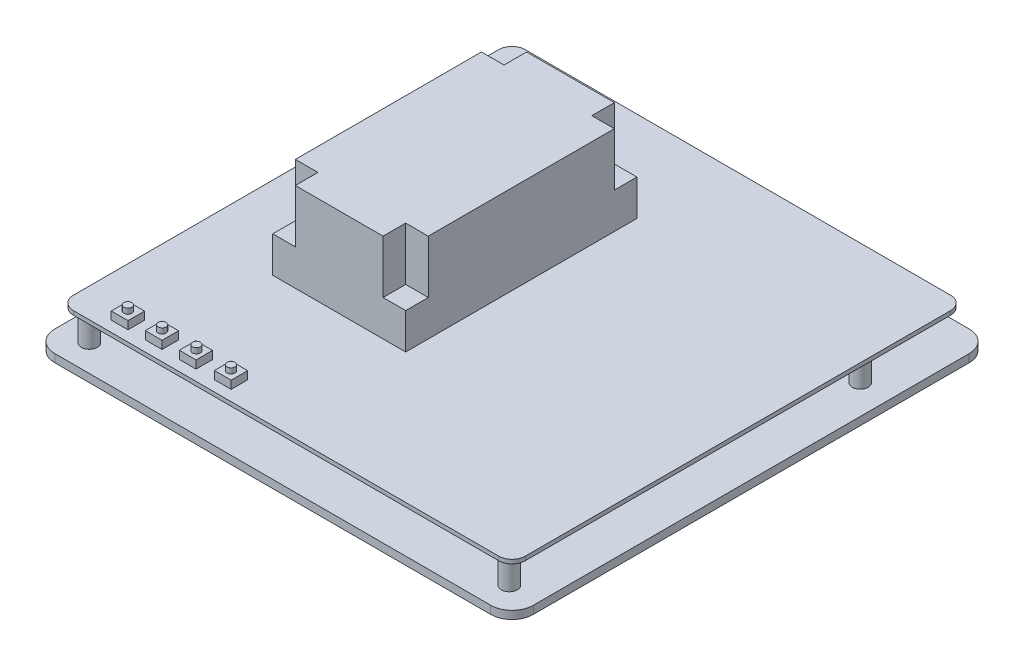
SolidWorks part; units mm, degrees
ref_plane "Plano frontal" through (0, 0, 0) normal (0, 0, 1) x (1, 0, 0)
ref_plane "Plano superior" through (0, 0, 0) normal (0, 1, 0) x (1, 0, 0)
ref_plane "Plano direito" through (0, 0, 0) normal (1, 0, 0) x (0, 0, -1)
sketch "Esboço1" plane through (0, 0, 0) normal (0, 1, 0) x (1, 0, 0)
  line L1 (82, -90) -> (-82, -90)
  line L2 (90, -82) -> (90, 82)
  line L3 (82, 90) -> (-82, 90)
  line L4 (-90, -82) -> (-90, 82)
  line L5 (90, -90) -> (-90, 90) construction
  line L6 (90, 90) -> (-90, -90) construction
  arc A0 (82, -90) -> (90, -82) centre (82, -82) ccw
  arc A1 (-82, -90) -> (-90, -82) centre (-82, -82) cw
  arc A2 (90, 82) -> (82, 90) centre (82, 82) ccw
  arc A3 (-82, 90) -> (-90, 82) centre (-82, 82) ccw
  point P0 (0, 0)
  dimension "D3" = 8
  dimension "D1" = 180
  dimension "D2" = 180
extrude "Ressalto-extrusão1" add sketch "Esboço1" along normal blind 3
sketch "Esboço2" plane through (0, 0, 0) normal (0, -1, 0) x (-1, 0, 0)
  line L0 (82, -90) -> (-82, -90) construction
  line L1 (90, 82) -> (90, -82) construction
  line L2 (0, 0) -> (-90, 0) construction
  line L3 (-90, -82) -> (-90, 82) construction
  line L4 (0, 0) -> (0, -90) construction
  circle A0 centre (79, -62) radius 3.5
  circle A1 centre (-79, -62) radius 3.5
  circle A2 centre (-79, 62) radius 3.5
  circle A3 centre (79, 62) radius 3.5
  dimension "D1" = 7
  dimension "D2" = 28
  dimension "D3" = 11
extrude "Ressalto-extrusão2" add sketch "Esboço2" along normal blind 5
sketch "Esboço3" plane through (0, 3, 0) normal (0, 1, 0) x (1, 0, 0)
  line L0 (90, -82) -> (90, 82) construction
  line L1 (-82, -90) -> (82, -90) construction
  line L2 (-90, 82) -> (-90, -82) construction
  line L3 (82, 90) -> (-82, 90) construction
  circle A0 centre (-79, -80) radius 3
  circle A1 centre (-79, 75) radius 3
  circle A2 centre (79, 52) radius 3
  circle A3 centre (79, -80) radius 3
  dimension "D1" = 6
  dimension "D3" = 11
  dimension "D5" = 10
  dimension "D6" = 38
  dimension "D2" = 10
  dimension "D4" = 11
  dimension "D7" = 15
extrude "Ressalto-extrusão3" add sketch "Esboço3" along normal blind 11
sketch "Esboço4" plane through (0, 14, 0) normal (0, 1, 0) x (1, 0, 0)
  line L1 (-80, 85) -> (80, 85)
  line L2 (-85, 80) -> (-85, -80)
  line L3 (-80, -85) -> (80, -85)
  line L4 (85, 80) -> (85, -80)
  line L5 (-85, 85) -> (85, -85) construction
  line L6 (-85, -85) -> (85, 85) construction
  arc A1 (80, -85) -> (85, -80) centre (80, -80) ccw
  arc A2 (-85, -80) -> (-80, -85) centre (-80, -80) ccw
  arc A3 (80, 85) -> (85, 80) centre (80, 80) cw
  arc A4 (-80, 85) -> (-85, 80) centre (-80, 80) ccw
  point P0 (0, 0)
  dimension "D3" = 5
  dimension "D1" = 170
  dimension "D2" = 170
extrude "Ressalto-extrusão4" add sketch "Esboço4" along normal blind 1.5
sketch "Esboço5" plane through (0, 15.5, 0) normal (0, 1, 0) x (1, 0, 0)
  line L0 (-80, -85) -> (80, -85) construction
  line L1 (-54, 51) -> (-4, 51)
  line L2 (-54, 51) -> (-54, -36)
  line L3 (-54, -36) -> (-4, -36)
  line L4 (-4, 51) -> (-4, -36)
  line L5 (-54, 51) -> (-4, -36) construction
  line L6 (-54, -36) -> (-4, 51) construction
  line L7 (-85, 80) -> (-85, -80) construction
  point P0 (-29, 7.5)
  point P5 (-51.8016, -21.9685)
  point P6 (-53.8976, -29.5663)
  dimension "D1" = 50
  dimension "D2" = 87
  dimension "D3" = 49
  dimension "D4" = 31
extrude "Ressalto-extrusão5" add sketch "Esboço5" along normal blind 33.5
sketch "Esboço6" plane through (0, 49, 0) normal (0, 1, 0) x (1, 0, 0)
  line L0 (-54, 7.5) -> (-4, 7.5) construction
  line L1 (-54, -36) -> (-45.5, -36)
  line L2 (-54, -36) -> (-54, -27.5)
  line L3 (-54, -27.5) -> (-45.5, -27.5)
  line L4 (-45.5, -36) -> (-45.5, -27.5)
  line L5 (-54, 51) -> (-54, -36) construction
  line L6 (-4, -36) -> (-4, 51) construction
  line L7 (-29, 51) -> (-29, -36) construction
  line L8 (-4, 51) -> (-54, 51) construction
  line L9 (-54, -36) -> (-4, -36) construction
  line L10 (-12.5, -36) -> (-12.5, -27.5)
  line L11 (-4, -36) -> (-12.5, -36)
  line L12 (-4, -36) -> (-4, -27.5)
  line L13 (-4, -27.5) -> (-12.5, -27.5)
  line L14 (-4, 42.5) -> (-12.5, 42.5)
  line L15 (-4, 51) -> (-4, 42.5)
  line L16 (-4, 51) -> (-12.5, 51)
  line L17 (-12.5, 51) -> (-12.5, 42.5)
  line L18 (-45.5, 51) -> (-45.5, 42.5)
  line L19 (-54, 42.5) -> (-45.5, 42.5)
  line L20 (-54, 51) -> (-54, 42.5)
  line L21 (-54, 51) -> (-45.5, 51)
  dimension "D1" = 8.5
  dimension "D2" = 8.5
extrude "Corte-extrusão1" cut sketch "Esboço6" against normal blind 20
sketch "Esboço7" plane through (0, 15.5, 0) normal (0, 1, 0) x (1, 0, 0)
  line L0 (-30.95, -74.8) -> (-24.65, -74.8)
  line L1 (-69.75, -74.8) -> (-63.45, -74.8)
  line L2 (-69.75, -74.8) -> (-69.75, -81)
  line L3 (-69.75, -81) -> (-63.45, -81)
  line L4 (-63.45, -74.8) -> (-63.45, -81)
  line L5 (-69.75, -74.8) -> (-63.45, -81) construction
  line L6 (-69.75, -81) -> (-63.45, -74.8) construction
  line L7 (-80, -85) -> (80, -85) construction
  line L8 (-85, 80) -> (-85, -80) construction
  line L9 (-56.95, -74.8) -> (-50.65, -74.8)
  line L10 (-56.95, -74.8) -> (-56.95, -81)
  line L11 (-56.95, -81) -> (-50.65, -81)
  line L12 (-50.65, -74.8) -> (-50.65, -81)
  line L13 (-56.95, -74.8) -> (-50.65, -81) construction
  line L14 (-56.95, -81) -> (-50.65, -74.8) construction
  line L15 (-44.15, -74.8) -> (-37.85, -74.8)
  line L16 (-44.15, -74.8) -> (-44.15, -81)
  line L17 (-44.15, -81) -> (-37.85, -81)
  line L18 (-37.85, -74.8) -> (-37.85, -81)
  line L19 (-44.15, -74.8) -> (-37.85, -81) construction
  line L20 (-44.15, -81) -> (-37.85, -74.8) construction
  line L21 (-30.95, -74.8) -> (-30.95, -81)
  line L22 (-30.95, -81) -> (-24.65, -81)
  line L23 (-24.65, -74.8) -> (-24.65, -81)
  line L24 (-30.95, -74.8) -> (-24.65, -81) construction
  line L25 (-30.95, -81) -> (-24.65, -74.8) construction
  point P0 (-66.6, -77.9)
  point P9 (0, 0)
  point P10 (-27.8, -77.9)
  point P11 (-53.8, -77.9)
  point P16 (-41, -77.9)
  point P22 (0, 0)
  point P26 (0, 0)
  dimension "D1" = 6.2
  dimension "D2" = 6.3
  dimension "D3" = 4
  dimension "D4" = 15.25
  dimension "D5" = 3
  dimension "D6" = 6.5
  dimension "D8" = 6.9
  dimension "D7" = 2
extrude "Ressalto-extrusão6" add sketch "Esboço7" along normal blind 3
sketch "Esboço8" plane through (0, 18.5, 0) normal (0, 1, 0) x (1, 0, 0)
  line L0 (-63.45, -81) -> (-63.45, -74.8) construction
  line L2 (-69.75, -81) -> (-63.45, -81) construction
  line L3 (-24.65, -81) -> (-24.65, -74.8) construction
  line L4 (-24.65, -74.8) -> (-30.95, -74.8) construction
  circle A0 centre (-66.6, -77.9) radius 1.5
  circle A1 centre (-53.7, -77.9) radius 1.5
  circle A2 centre (-40.8, -77.9) radius 1.5
  circle A3 centre (-27.75, -77.95) radius 1.5
  point P6 (-66.6, -81)
  point P17 (0, 0)
  dimension "D1" = 3.15
  dimension "D2" = 3.1
  dimension "D3" = 3
  dimension "D5" = 3
  dimension "D6" = 3.1
  dimension "D7" = 3.15
  dimension "D8" = 12.9
  dimension "D4" = 3
extrude "Ressalto-extrusão7" add sketch "Esboço8" along normal blind 2
